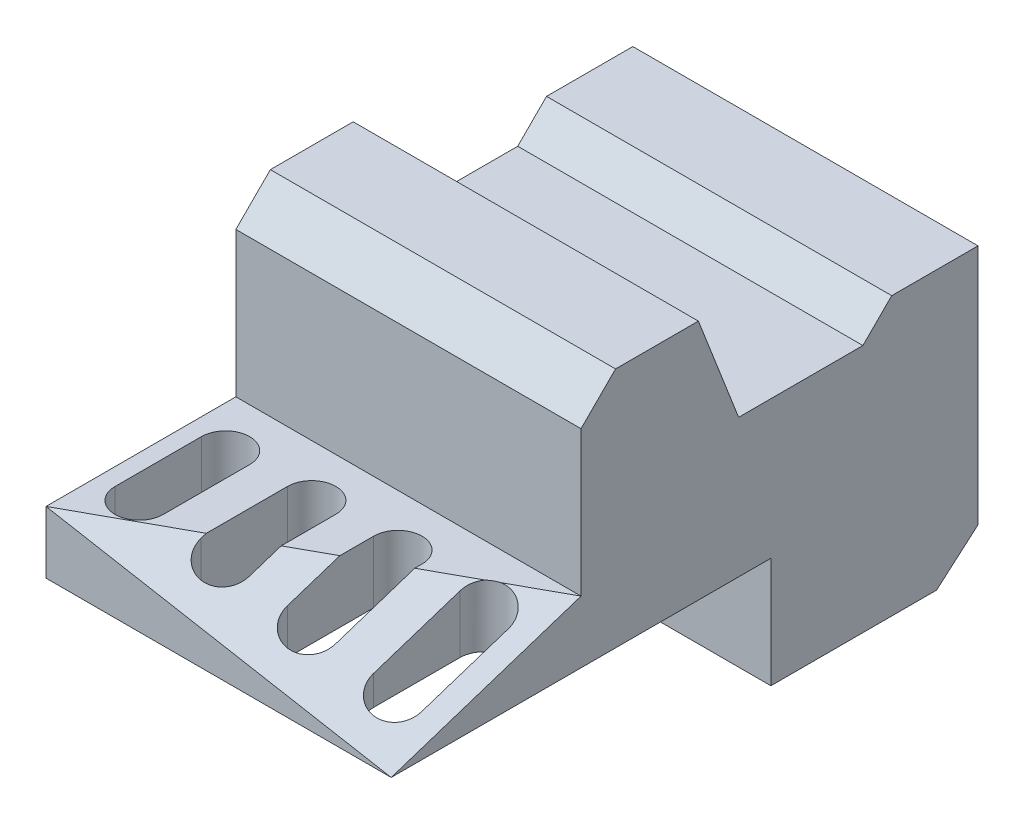
SolidWorks part; units mm, degrees
ref_plane "Plano frontal" through (0, 0, 0) normal (0, 0, 1) x (1, 0, 0)
ref_plane "Plano superior" through (0, 0, 0) normal (0, 1, 0) x (1, 0, 0)
ref_plane "Plano direito" through (0, 0, 0) normal (1, 0, 0) x (0, 0, -1)
sketch "Esboço3" plane through (0, 0, 0) normal (1, 0, 0) x (0, 0, -1)
  line L0 (0, 0) -> (0, -70)
  line L1 (0, 0) -> (-25, 0)
  line L2 (-12, -80.38) -> (-60, -80.38)
  line L3 (-25, 0) -> (-33.3439, -8.3439)
  line L4 (-33.3439, -8.3439) -> (-69.3439, -8.3439)
  line L5 (-60, -80.38) -> (-60, -48.3785)
  line L6 (-69.3439, -8.3439) -> (-81.0015, 21.62)
  line L7 (-81.0015, 21.62) -> (-105.0015, 21.62)
  line L8 (-105.0015, 21.62) -> (-115, 11.6215)
  line L9 (-115, 11.6215) -> (-115, -30.3785)
  line L10 (-115, -30.3785) -> (-170, -30.3785)
  line L11 (-170, -30.3785) -> (-170, -48.3785)
  line L12 (-170, -48.3785) -> (-60, -48.3785)
  line L13 (0, -70) -> (-12, -80.38)
  point P5 (0, -70)
  point P8 (-12, -80.38)
  dimension "D1" = 18
  dimension "D2" = 25
  dimension "D3" = 55
  dimension "D4" = 11.8
  dimension "D5" = 36
  dimension "D6" = 110
  dimension "D7" = 102
  dimension "D8" = 42
  dimension "D9" = 14.14
  dimension "D10" = 24
  dimension "D11" = 80.38
  dimension "D12" = 70
  dimension "D13" = 158
extrude "Ressalto-extrusão1" add sketch "Esboço3" along normal blind 100
sketch "Esboço5" plane through (0, -30.3785, 0) normal (0, 1, 0) x (1, 0, 0)
  line L0 (0, -142.5) -> (100, -142.5) construction
  line L1 (0, -115) -> (0, -170) construction
  line L2 (100, -115) -> (100, -170) construction
  line L3 (12, -155.02) -> (12, -129.98) construction
  line L4 (5, -155.02) -> (5, -129.98)
  line L5 (19, -155.02) -> (19, -129.98)
  line L6 (36.96, -155.02) -> (36.96, -129.98) construction
  line L7 (29.96, -155.02) -> (29.96, -129.98)
  line L8 (43.96, -155.02) -> (43.96, -129.98)
  line L9 (61.92, -155.02) -> (61.92, -129.98) construction
  line L10 (54.92, -155.02) -> (54.92, -129.98)
  line L11 (68.92, -155.02) -> (68.92, -129.98)
  line L12 (86.88, -155.02) -> (86.88, -129.98) construction
  line L13 (79.88, -155.02) -> (79.88, -129.98)
  line L14 (93.88, -155.02) -> (93.88, -129.98)
  line L15 (12, -155.02) -> (36.96, -155.02) construction
  arc A0 (5, -155.02) -> (19, -155.02) centre (12, -155.02) ccw
  arc A1 (19, -129.98) -> (5, -129.98) centre (12, -129.98) ccw
  arc A2 (29.96, -155.02) -> (43.96, -155.02) centre (36.96, -155.02) ccw
  arc A3 (43.96, -129.98) -> (29.96, -129.98) centre (36.96, -129.98) ccw
  arc A4 (54.92, -155.02) -> (68.92, -155.02) centre (61.92, -155.02) ccw
  arc A5 (68.92, -129.98) -> (54.92, -129.98) centre (61.92, -129.98) ccw
  arc A6 (79.88, -155.02) -> (93.88, -155.02) centre (86.88, -155.02) ccw
  arc A7 (93.88, -129.98) -> (79.88, -129.98) centre (86.88, -129.98) ccw
  point P8 (12, -142.5)
  point P16 (36.96, -142.5)
  point P23 (61.92, -142.5)
  point P30 (86.88, -142.5)
  dimension "D1" = 12.52
  dimension "D2" = 7
  dimension "D3" = 5
  dimension "D5" = 24.96
  dimension "D4" = 4
extrude "Corte-extrusão1" cut sketch "Esboço5" against normal through all
ref_plane "Plano1" through (3.9898, 22.1656, 7.2542) normal (0.1686, 0.9368, 0.3066) x (0.9857, -0.1603, -0.0524)
sketch "Esboço6" plane through (3.9898, 22.1656, 7.2542) normal (0.1686, 0.9368, 0.3066) x (0.9857, -0.1603, -0.0524)
  line L0 (-4.0478, -171.0164) -> (97.405, -176.6151)
  line L1 (97.405, -176.6151) -> (97.405, -118.7446)
  line L2 (97.405, -118.7446) -> (-4.0478, -171.0164)
extrude "Corte-extrusão4" cut sketch "Esboço6" along normal blind 87
